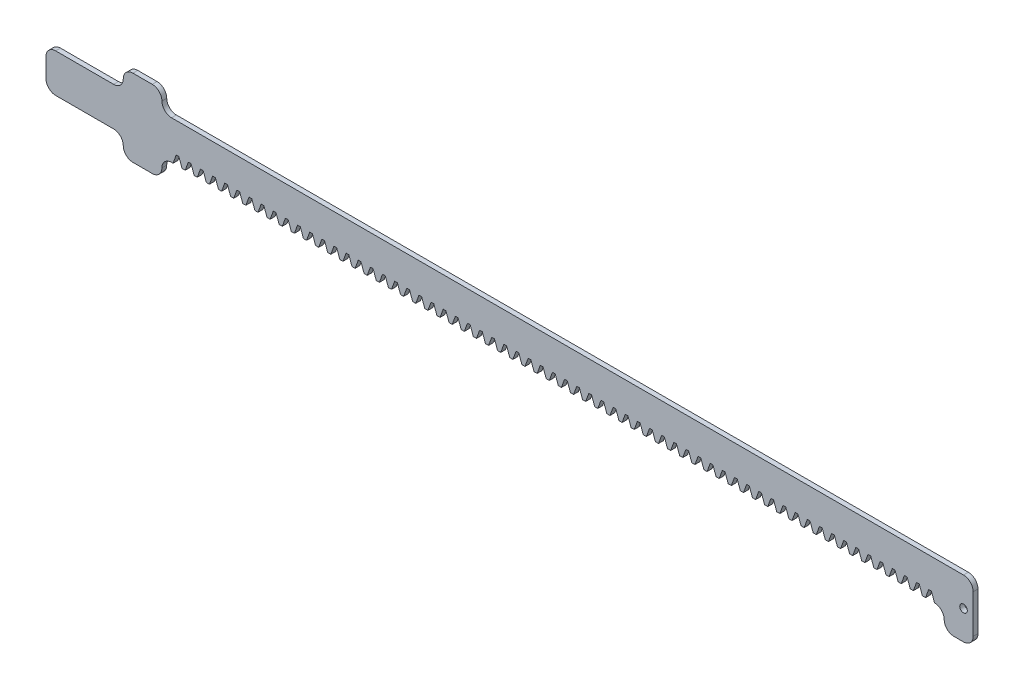
SolidWorks part; units mm, degrees
material "PC High Viscosity"
ref_plane "Front Plane" through (0, 0, 0) normal (0, 0, 1) x (1, 0, 0)
ref_plane "Top Plane" through (0, 0, 0) normal (0, 1, 0) x (1, 0, 0)
ref_plane "Right Plane" through (0, 0, 0) normal (1, 0, 0) x (0, 0, -1)
sketch "Sketch1" plane through (0, 0, 0) normal (0, 0, 1) x (1, 0, 0)
  line L0 (50.8, 0) -> (50.8, -12.7)
  line L1 (0, 0) -> (590.55, 0)
  line L2 (0, 0) -> (0, 25.4)
  line L3 (0, 25.4) -> (609.6, 25.4)
  line L4 (609.6, 0) -> (609.6, 25.4)
  line L5 (50.8, 38.1) -> (76.2, 38.1)
  line L6 (76.2, 38.1) -> (76.2, 25.4)
  line L7 (50.8, 38.1) -> (50.8, 25.4)
  line L8 (76.2, 0) -> (76.2, -12.7)
  line L9 (76.2, -12.7) -> (50.8, -12.7)
  line L10 (590.55, 0) -> (590.55, -12.7)
  line L11 (609.6, 10.0162) -> (603.25, 13.6823) construction
  line L12 (603.25, 13.6823) -> (596.9, 10.0162) construction
  line L13 (596.9, 10.0162) -> (596.9, 2.6838) construction
  line L14 (596.9, 2.6838) -> (603.25, -0.9823) construction
  line L15 (603.25, -0.9823) -> (609.6, 2.6838) construction
  line L16 (609.6, 2.6838) -> (609.6, 10.0162) construction
  line L17 (609.6, 0) -> (609.6, -12.7)
  line L18 (609.6, -12.7) -> (590.55, -12.7)
  circle A0 centre (603.25, 6.35) radius 2.4892
  circle A1 centre (603.25, 6.35) radius 6.35 construction
  dimension "D5" = 4.9784
  dimension "D6" = 12.7
  dimension "D7" = 12.7
  dimension "D1" = 609.6
  dimension "D2" = 25.4
  dimension "D3" = 25.4
  dimension "D4" = 50.8
  dimension "D8" = 19.05
  dimension "D9" = 12.7
extrude "Boss-Extrude1" add sketch "Sketch1" along normal blind 3.175 contours L6 L5 L3 | L1 L4 L3 L2 A0 | L9 L8 L1 region at (63.5, -6.35, 0) region at (308.9784, 12.4144, 0) region at (63.5, 31.75, 0)
fillet "Fillet2" radius 6.35 14 edges at (76.2, 38.1, 1.5875) (76.2, 25.4, 1.5875) (609.6, 25.4, 1.5875) (76.2, 0, 1.5875) (76.2, -12.7, 1.5875) (50.8, -12.7, 1.5875) (50.8, 0, 1.5875) (0, 0, 1.5875) (50.8, 38.1, 1.5875) (50.8, 25.4, 1.5875) (0, 25.4, 1.5875) (590.55, 0, 1.5875) (590.55, -12.7, 1.5875) (609.6, -12.7, 1.5875)
sketch "Sketch2" plane through (0, 0, 3.175) normal (0, 0, 1) x (1, 0, 0)
  line L0 (584.2, 0) -> (82.55, 0)
  line L1 (82.55, 0) -> (82.55, 5.715)
  line L2 (82.55, 5.715) -> (584.2, 5.715)
  line L3 (584.2, 5.715) -> (584.2, 0)
  line L5 (583.2755, 2.54) -> (575.111, 2.54) construction
  line L6 (584.2, 0) -> (582.1199, 5.715)
  line L7 (82.55, 0) -> (584.2, 0) construction
  line L8 (578.2688, 0) -> (584.2, 0)
  line L9 (579.389, 0) -> (584.2, 0)
  line L10 (582.1199, 5.715) -> (580.3488, 5.715)
  line L11 (584.2, 0) -> (578.2688, 0)
  line L12 (578.2688, 0) -> (580.3488, 5.715)
  line L13 (580.3488, 5.715) -> (582.1199, 5.715)
  line L14 (584.2, 0) -> (578.2688, 0)
  line L15 (580.3488, 5.715) -> (582.1199, 5.715)
  line L16 (584.2, 0) -> (578.2688, 0)
  line L17 (578.2688, 0) -> (576.0355, 0)
  line L19 (582.1199, 5.715) -> (580.3488, 5.715) construction
  line L20 (578.2688, 0) -> (576.0355, 0) construction
  point P8 (579.1932, 2.54)
  point P16 (583.2755, 2.54)
  point P17 (575.111, 2.54)
  point P19 (580.5612, 5.715)
  point P20 (0, 0)
  dimension "D1" = 70
  dimension "D2" = 2.54
  dimension "D3" = 3.175
  dimension "D4" = 70
  dimension "D5" = 1.7711
extrude "Cut-Extrude1" cut sketch "Sketch2" against normal through all contours L12 L0 L8 L6 L2 region at (581.2344, 2.343, 3.175)
pattern_linear "LPattern1" count 63 spacing 7.9796 along (-1, 0, 0) of "Cut-Extrude1"
